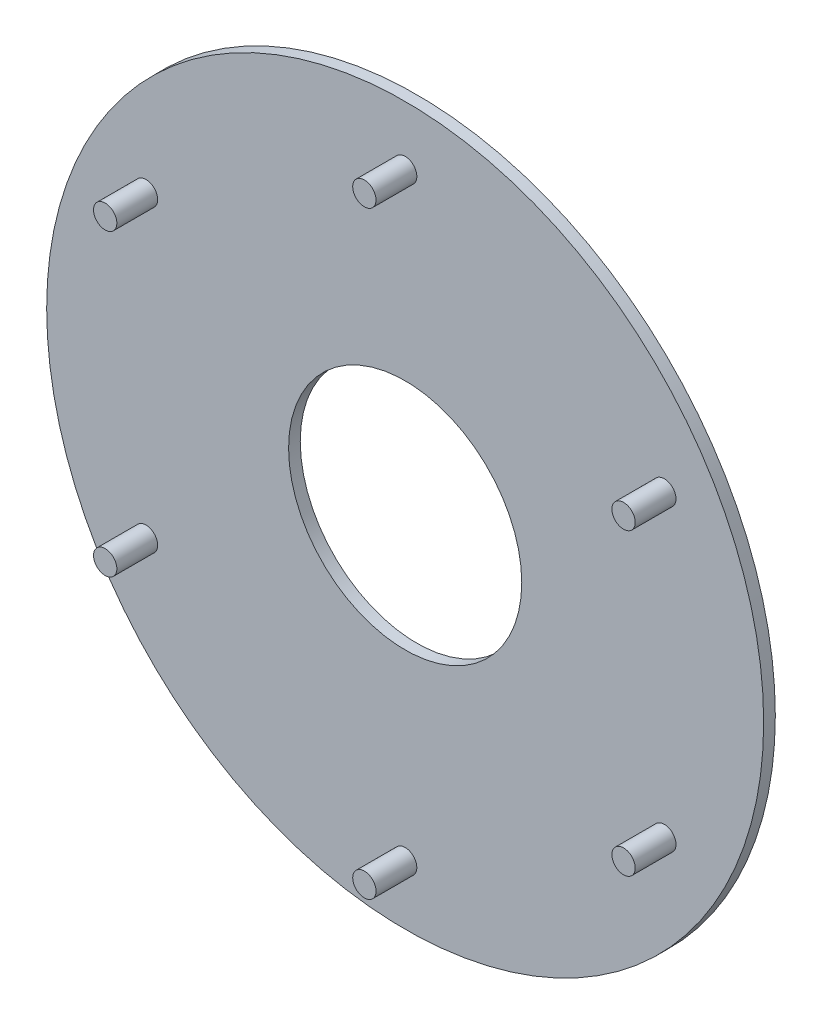
SolidWorks part; units mm, degrees
material "AISI 316 Stainless Steel Sheet (SS)"
ref_plane "Front Plane" through (0, 0, 0) normal (0, 0, 1) x (1, 0, 0)
ref_plane "Top Plane" through (0, 0, 0) normal (0, 1, 0) x (1, 0, 0)
ref_plane "Right Plane" through (0, 0, 0) normal (1, 0, 0) x (0, 0, -1)
sketch "Sketch1" plane through (0, 0, 0) normal (0, 0, 1) x (1, 0, 0)
  circle A0 centre (0, 0) radius 20
  circle A1 centre (0, 0) radius 61.5
  circle A2 centre (0, 0) radius 59.5 construction
  circle A3 centre (0, 0) radius 22 construction
  dimension "D1" = 40
  dimension "D2" = 123
  dimension "D3" = 2
  dimension "D4" = 2
extrude "Boss-Extrude1" add sketch "Sketch1" against normal blind 2 contours A1
sketch "Sketch2" plane through (0, 0, 0) normal (0, 0, 1) x (1, 0, 0)
  circle A0 centre (0, 51.3383) radius 2
  dimension "D1" = 4
extrude "Boss-Extrude2" add sketch "Sketch2" along normal blind 7
sketch "Sketch4" plane through (0, 0, 0) normal (1, 0, 0) x (0, 0, -1)
  line L0 (0, 0) -> (50000, 0) construction
pattern_circular "CirPattern1" count 6 over 360 about axis through (0, 0, 0) along (0, 0, -1) of "Boss-Extrude2"
extrude "Cut-Extrude1" cut sketch "Sketch1<3>" against normal through all contours A0 region at (0, 0, 0)
sketch "Sketch1<3>" plane through (0, 0, 0) normal (0, 0, 1) x (1, 0, 0) same geometry as "Sketch1"
